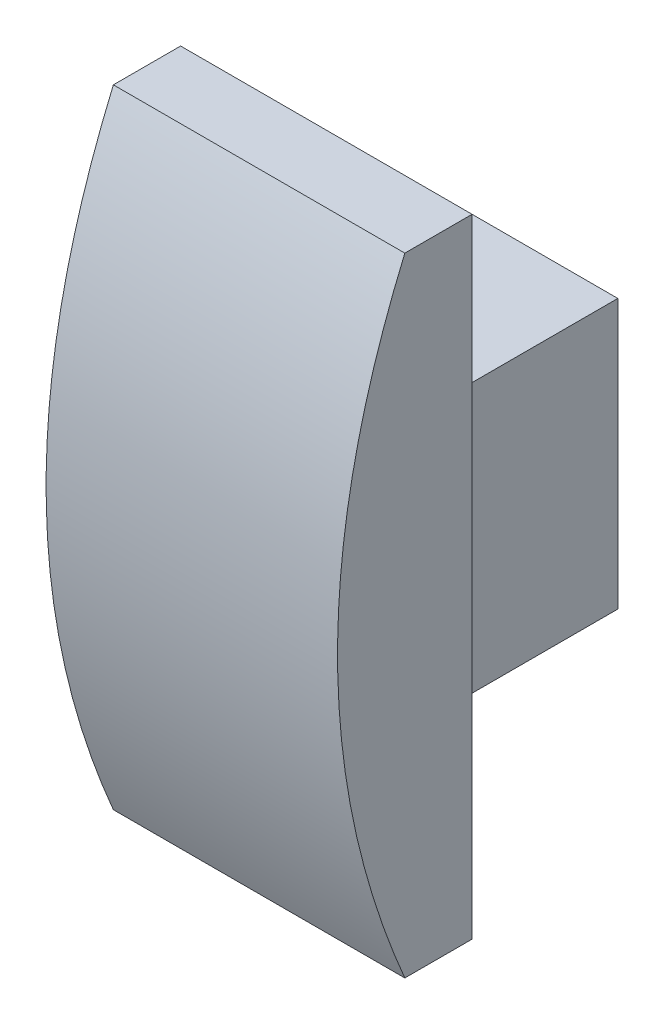
SolidWorks part; units mm, degrees
ref_plane "Płaszczyzna przednia" through (0, 0, 0) normal (0, 0, 1) x (1, 0, 0)
ref_plane "Płaszczyzna górna" through (0, 0, 0) normal (0, 1, 0) x (1, 0, 0)
ref_plane "Płaszczyzna prawa" through (0, 0, 0) normal (1, 0, 0) x (0, 0, -1)
sketch "Szkic1" plane through (0, 0, 0) normal (0, 0, 1) x (1, 0, 0)
  line L0 (0, -1.05) -> (2.1, -1.05) construction
  line L1 (0, 0) -> (2.1, 0)
  line L2 (0, 0) -> (0, -2.1)
  line L3 (0, -2.1) -> (2.1, -2.1)
  line L4 (2.1, 0) -> (2.1, -2.1)
  line L5 (-1.45, 1.95) -> (3.55, 1.95)
  line L6 (-1.45, 1.95) -> (-1.45, -4.05)
  line L7 (-1.45, -4.05) -> (3.55, -4.05)
  line L8 (3.55, 1.95) -> (3.55, -4.05)
  line L9 (1.05, 0) -> (1.05, -2.1) construction
  point P9 (1.05, -4.05)
  dimension "D1" = 2.1
  dimension "D2" = 2.1
  dimension "D3" = 5
  dimension "D4" = 6
extrude "Dodanie-wyciągnięcie1" add sketch "Szkic1" along normal blind 4
sketch "Szkic3" plane through (0, 0, 4) normal (0, 0, 1) x (1, 0, 0)
  line L0 (0, -1.05) -> (2.1, -1.05) construction
  line L1 (-2.2, 5.95) -> (4.3, 5.95)
  line L2 (-2.2, 5.95) -> (-2.2, -8.05)
  line L3 (-2.2, -8.05) -> (4.3, -8.05)
  line L4 (4.3, 5.95) -> (4.3, -8.05)
  line L5 (-1.45, -4.05) -> (3.55, -4.05) construction
  line L7 (1.05, 0) -> (1.05, -2.1) construction
  dimension "D1" = 4
  dimension "D2" = 6.5
extrude "Dodanie-wyciągnięcie2" add sketch "Szkic3" along normal blind 3
sketch "Szkic4" plane through (-2.2, 0, 0) normal (-1, 0, 0) x (0, 0, 1)
  line L2 (7, 5.95) -> (4, 5.95) construction
  line L3 (7, 5.95) -> (7, -8.05) construction
  line L4 (7, -8.05) -> (4, -8.05) construction
  line L5 (5.5, 5.95) -> (7, 5.95)
  line L6 (7, 5.95) -> (7, -8.05)
  line L7 (7, -8.05) -> (5.5, -8.05)
  spline S0 degree 2 poles (5.5, 5.95) (8.5, -1.05) (5.5, -8.05) knots 0 0 0 1 1 1
  line M2 (4, -8.05) -> (7, -8.05)
  line M3 (7, -8.05) -> (7, 5.95)
  line M4 (7, 5.95) -> (4, 5.95)
extrude "Wytnij-wyciągnięcie1" cut sketch "Szkic4" against normal through all contours S0 M3 M2 | S0 L6 M4 region at (-2.2, -6.3, 6.55) region at (-2.2, 4.2, 6.55)
